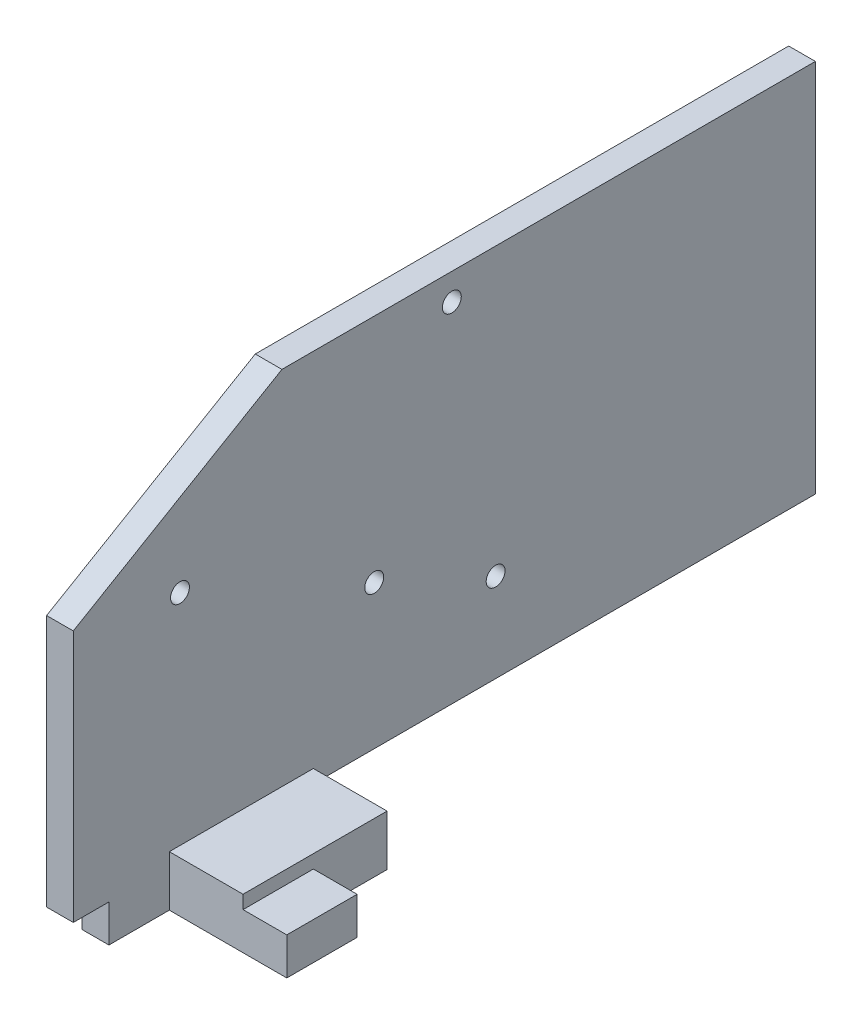
SolidWorks part; units mm, degrees
material "BRASS"
ref_plane "Front Plane" through (0, 0, 0) normal (0, 0, 1) x (1, 0, 0)
ref_plane "Top Plane" through (0, 0, 0) normal (0, 1, 0) x (1, 0, 0)
ref_plane "Right Plane" through (0, 0, 0) normal (1, 0, 0) x (0, 0, -1)
sketch "Sketch2" plane through (0, 0, 0) normal (1, 0, 0) x (0, 0, -1)
  line L6 (0, 0) -> (76.2, 0)
  line L7 (76.2, 0) -> (176.67, 0)
  line L10 (49.67, 89.2048) -> (0, 60.1162)
  line L12 (49.67, 89.2048) -> (176.67, 89.2048)
  line L13 (176.67, 89.2048) -> (176.67, 0)
  line L15 (0, 60.1162) -> (0, 0)
  line L16 (22.86, 0) -> (22.86, 3.175)
  line L17 (57.15, 0) -> (57.15, 3.175)
  line L18 (44.45, 0) -> (44.45, 3.175) construction
  line L19 (31.75, 0) -> (31.75, 3.175) construction
  line L20 (22.86, 3.175) -> (57.15, 3.175)
  line L21 (57.15, 0) -> (57.15, -8.89)
  line L22 (57.15, -8.89) -> (8.4806, -8.89)
  line L24 (8.4806, -8.89) -> (8.4806, 0)
  line L25 (22.86, 0) -> (22.86, -8.89)
  line L26 (25.4, 55.3212) -> (71.6421, 34.29) construction
  line L27 (71.6421, 34.29) -> (100.5434, 21.1455) construction
  circle A0 centre (25.4, 55.3212) radius 2.2479
  circle A1 centre (90.1192, 82.8548) radius 2.2479
  circle A3 centre (25.4, 55.3212) radius 50.8 construction
  circle A4 centre (71.6421, 34.29) radius 31.75 construction
  circle A5 centre (71.6421, 34.29) radius 2.2479
  circle A6 centre (100.5434, 21.1455) radius 2.2479
  point P22 (0, 0)
  point P23 (176.67, 0)
  point P30 (71.6421, 34.29)
  dimension "D3" = 4.4958
  dimension "D14" = 101.6
  dimension "D16" = 63.5
  dimension "D17" = 4.4958
  dimension "D1" = 76.2
  dimension "D2" = 25.4
  dimension "D4" = 55.3212
  dimension "D5" = 82.8548
  dimension "D6" = 70.3326
  dimension "D7" = 40.4492
  dimension "D8" = 6.35
  dimension "D9" = 3.175
  dimension "D10" = 12.7
  dimension "D11" = 19.05
  dimension "D12" = 8.89
  dimension "D13" = 12.7
  dimension "D15" = 34.29
  dimension "D18" = 8.89
  dimension "D19" = 127
extrude "Boss-Extrude3" add sketch "Sketch2" against normal blind 6.35 contours L20 L16 L6 L17 | L16 L20 L17 L6 L7 L13 L12 L10 L15 A1 A0 | L6 L25 L22 L21 | L25 L6 L24 L22 region at (0, 43.2048, -92.2474) region at (0, -4.445, -15.6703) region at (0, 1.5875, -40.005) region at (0, -4.445, -40.005)
extrude "Boss-Extrude4" add sketch "Sketch2<5>" along normal blind 17.5514 contours L20 L16 L6 L17 | L6 L25 L22 L21 region at (0, 1.5875, -40.005) region at (0, -4.445, -40.005)
sketch "Sketch2<5>" plane through (0, 0, 0) normal (1, 0, 0) x (0, 0, -1) same geometry as "Sketch2"
sketch "Sketch3" plane through (17.5514, 0, 0) normal (1, 0, 0) x (0, 0, -1)
  line L0 (39.6, 0) -> (39.6, -8.89)
  line L1 (57.15, -8.89) -> (22.86, -8.89) construction
  line L2 (39.6, 0) -> (39.6, -7.4092) construction
  line L3 (39.6, -8.89) -> (22.86, -8.89)
  line L4 (22.86, -8.89) -> (22.86, 0)
  line L5 (22.86, -8.89) -> (22.86, 3.175) construction
  line L6 (22.86, 0) -> (39.6, 0)
extrude "Boss-Extrude5" add sketch "Sketch3" along normal blind 10.414
